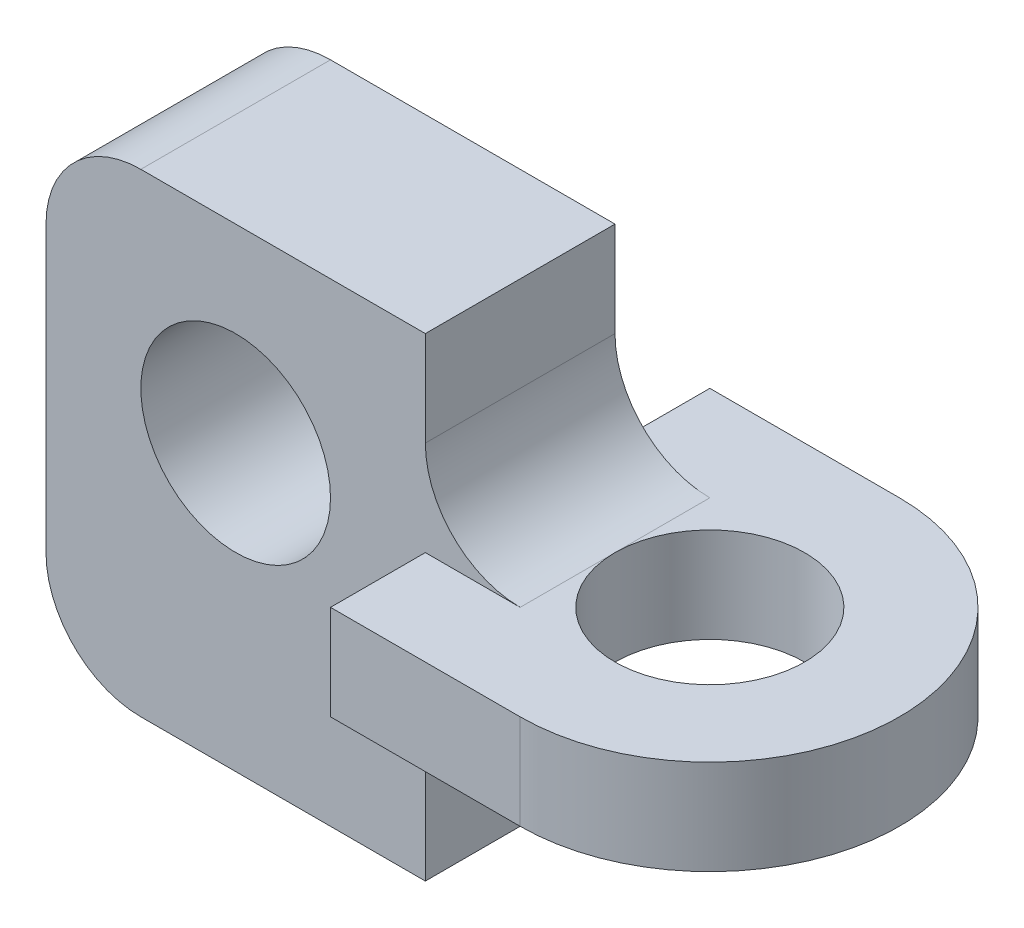
SolidWorks part; units mm, degrees
ref_plane "前基準面" through (0, 0, 0) normal (0, 0, 1) x (1, 0, 0)
ref_plane "上基準面" through (0, 0, 0) normal (0, 1, 0) x (1, 0, 0)
ref_plane "右基準面" through (0, 0, 0) normal (1, 0, 0) x (0, 0, -1)
sketch "草圖1" plane through (0, 0, 0) normal (0, 0, 1) x (1, 0, 0)
  line L0 (0, -5) -> (0, -25)
  line L1 (-30, 25) -> (0, 25)
  line L2 (-40, 15) -> (-40, -15)
  line L3 (-30, -25) -> (0, -25)
  line L4 (0, 25) -> (0, 5)
  line L5 (0, 5) -> (10, 5)
  line L7 (0, -5) -> (10, -5)
  line L8 (10, 5) -> (10, -5)
  circle A0 centre (-20, 5) radius 10
  arc A1 (-40, -15) -> (-30, -25) centre (-30, -15) ccw
  arc A2 (-30, 25) -> (-40, 15) centre (-30, 15) ccw
  point P4 (-40, 0)
  point P8 (10, 0)
  point P12 (-40, -25)
  point P15 (-40, 25)
  dimension "D3" = 20
  dimension "D5" = 10
  dimension "D1" = 50
  dimension "D2" = 40
  dimension "D4" = 20
  dimension "D6" = 20
  dimension "D7" = 10
  dimension "D8" = 10
extrude "填料-伸長1" add sketch "草圖1" along normal mid plane 20
fillet "圓角1" radius 10 2 edges at (0, -5, 0) (0, 5, 0)
sketch "草圖2" plane through (0, 0, 0) normal (0, 1, 0) x (1, 0, 0)
  line L0 (10, -10) -> (10, 10) construction
  line L1 (20, 20) -> (0, 20)
  line L2 (0, 20) -> (0, -20)
  line L3 (0, -20) -> (20, -20)
  arc A0 (20, -20) -> (20, 20) centre (20, 0) ccw
  circle A1 centre (20, 0) radius 10
  point P1 (40, 0)
  dimension "D1" = 40
  dimension "D2" = 20
  dimension "D3" = 10
extrude "填料-伸長2" add sketch "草圖2" along normal mid plane 10
